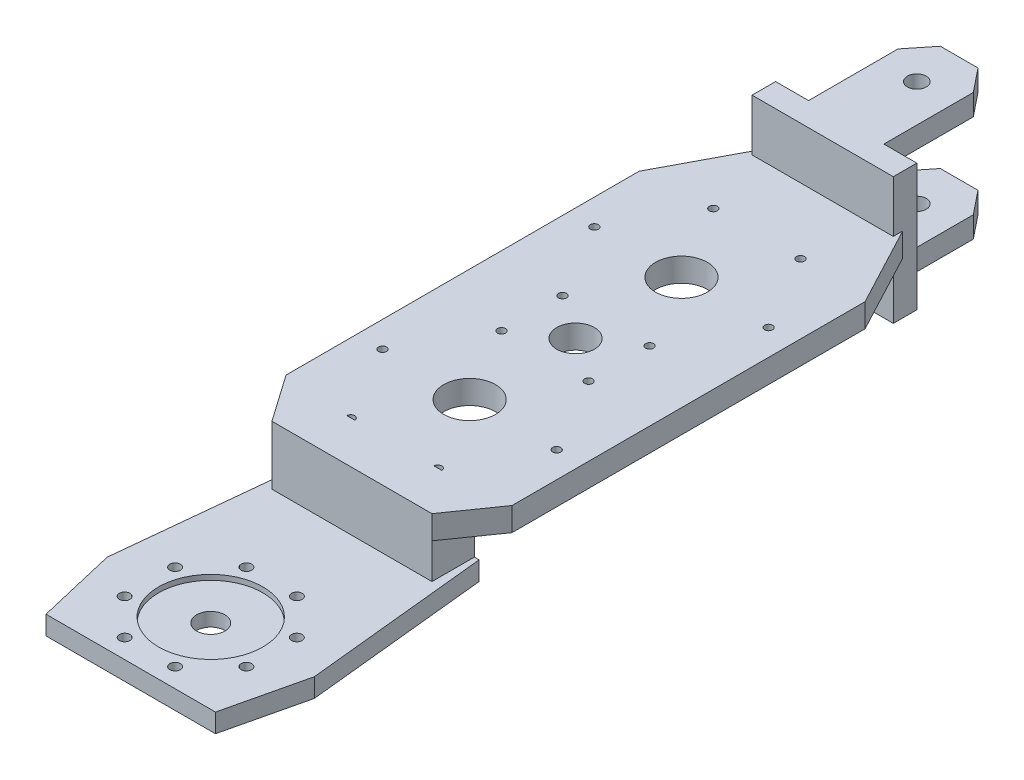
SolidWorks part; units mm, degrees
ref_plane "Front Plane" through (0, 0, 0) normal (0, 0, 1) x (1, 0, 0)
ref_plane "Top Plane" through (0, 0, 0) normal (0, 1, 0) x (1, 0, 0)
ref_plane "Right Plane" through (0, 0, 0) normal (1, 0, 0) x (0, 0, -1)
ref_plane "PL_Knee_Plate_base" through (0, -28, 0) normal (0, 1, 0) x (1, 0, 0)
sketch "SK_Knee_Plate" plane through (0, -28, 0) normal (0, 1, 0) x (1, 0, 0)
  line L0 (-36, -34) -> (36, -34)
  line L1 (36, -34) -> (44, 0)
  line L2 (44, 0) -> (36, 78)
  line L3 (36, 78) -> (-36, 78)
  line L4 (-36, 78) -> (-44, 0)
  line L5 (-44, 0) -> (-36, -34)
  circle A0 centre (25.8686, 10.7151) radius 2.25
  circle A1 centre (10.7151, 25.8686) radius 2.25
  circle A2 centre (-10.7151, 25.8686) radius 2.25
  circle A3 centre (-25.8686, 10.7151) radius 2.25
  circle A4 centre (-25.8686, -10.7151) radius 2.25
  circle A5 centre (-10.7151, -25.8686) radius 2.25
  circle A6 centre (10.7151, -25.8686) radius 2.25
  circle A7 centre (25.8686, -10.7151) radius 2.25
  circle A8 centre (0, 0) radius 6
  dimension "D11_SK_Knee_Plate" = 4.5
  dimension "D14_SK_Knee_Plate" = 4.5
  dimension "D17_SK_Knee_Plate" = 4.5
  dimension "D20_SK_Knee_Plate" = 4.5
  dimension "D23_SK_Knee_Plate" = 4.5
  dimension "D26_SK_Knee_Plate" = 4.5
  dimension "D29_SK_Knee_Plate" = 4.5
  dimension "D32_SK_Knee_Plate" = 4.5
  dimension "D35_SK_Knee_Plate" = 12
  dimension "P1" = 36
  dimension "P2" = 34
  dimension "P3" = 36
  dimension "P4" = 34
  dimension "P5" = 44
  dimension "P6" = 36
  dimension "P7" = 78
  dimension "P8" = 36
  dimension "P9" = 78
  dimension "P10" = 44
  dimension "P12" = 25.8686
  dimension "P13" = 10.7151
  dimension "P15" = 10.7151
  dimension "P16" = 25.8686
  dimension "P18" = 10.7151
  dimension "P19" = 25.8686
  dimension "P21" = 25.8686
  dimension "P22" = 10.7151
  dimension "P24" = 25.8686
  dimension "P25" = 10.7151
  dimension "P27" = 10.7151
  dimension "P28" = 25.8686
  dimension "P30" = 10.7151
  dimension "P31" = 25.8686
  dimension "P33" = 25.8686
  dimension "P34" = 10.7151
extrude "Knee_Plate" add sketch "SK_Knee_Plate" along normal blind 8
ref_plane "PL_Knee_Pilot_Recess_base" through (0, -20, 0) normal (0, 1, 0) x (1, 0, 0)
sketch "SK_Knee_Pilot_Recess" plane through (0, -20, 0) normal (0, 1, 0) x (1, 0, 0)
  circle A0 centre (0, 0) radius 22.15
  dimension "D1_SK_Knee_Pilot_Recess" = 44.3
extrude "Knee_Pilot_Recess" cut sketch "SK_Knee_Pilot_Recess" against normal blind 2.2
ref_plane "PL_Joggle_base" through (0, 0, -78) normal (0, 0, 1) x (1, 0, 0)
sketch "SK_Joggle" plane through (0, 0, -78) normal (0, 0, 1) x (1, 0, 0)
  line L0 (-34, -28) -> (34, -28)
  line L1 (34, -28) -> (34, 5)
  line L2 (34, 5) -> (-34, 5)
  line L3 (-34, 5) -> (-34, -28)
  dimension "P1" = 34
  dimension "P2" = 28
  dimension "P3" = 34
  dimension "P4" = 28
  dimension "P5" = 34
  dimension "P6" = 5
  dimension "P7" = 34
  dimension "P8" = 5
extrude "Joggle" add sketch "SK_Joggle" along normal blind 18
ref_plane "PL_Web_base" through (0, -5, 0) normal (0, 1, 0) x (1, 0, 0)
sketch "SK_Web" plane through (0, -5, 0) normal (0, 1, 0) x (1, 0, 0)
  line L0 (-34, 60) -> (34, 60)
  line L1 (34, 60) -> (48, 80)
  line L2 (48, 80) -> (48, 230)
  line L3 (48, 230) -> (30, 264)
  line L4 (30, 264) -> (-30, 264)
  line L5 (-30, 264) -> (-48, 230)
  line L6 (-48, 230) -> (-48, 80)
  line L7 (-48, 80) -> (-34, 60)
  circle A0 centre (37, 110) radius 1.7
  circle A1 centre (18.5, 142.0429) radius 1.7
  circle A2 centre (-18.5, 142.0429) radius 1.7
  circle A3 centre (-37, 110) radius 1.7
  circle A4 centre (-18.5, 77.9571) radius 1.7
  circle A5 centre (18.5, 77.9571) radius 1.7
  circle A6 centre (37, 200) radius 1.7
  circle A7 centre (18.5, 232.0429) radius 1.7
  circle A8 centre (-18.5, 232.0429) radius 1.7
  circle A9 centre (-37, 200) radius 1.7
  circle A10 centre (-18.5, 167.9571) radius 1.7
  circle A11 centre (18.5, 167.9571) radius 1.7
  circle A12 centre (0, 110) radius 11
  circle A13 centre (0, 200) radius 11
  circle A14 centre (0, 155) radius 8
  dimension "D17_SK_Web" = 3.4
  dimension "D20_SK_Web" = 3.4
  dimension "D23_SK_Web" = 3.4
  dimension "D26_SK_Web" = 3.4
  dimension "D29_SK_Web" = 3.4
  dimension "D32_SK_Web" = 3.4
  dimension "D35_SK_Web" = 3.4
  dimension "D38_SK_Web" = 3.4
  dimension "D41_SK_Web" = 3.4
  dimension "D44_SK_Web" = 3.4
  dimension "D47_SK_Web" = 3.4
  dimension "D50_SK_Web" = 3.4
  dimension "D53_SK_Web" = 22
  dimension "D55_SK_Web" = 22
  dimension "D57_SK_Web" = 16
  dimension "P1" = 34
  dimension "P2" = 60
  dimension "P3" = 34
  dimension "P4" = 60
  dimension "P5" = 48
  dimension "P6" = 80
  dimension "P7" = 48
  dimension "P8" = 230
  dimension "P9" = 30
  dimension "P10" = 264
  dimension "P11" = 30
  dimension "P12" = 264
  dimension "P13" = 48
  dimension "P14" = 230
  dimension "P15" = 48
  dimension "P16" = 80
  dimension "P18" = 37
  dimension "P19" = 110
  dimension "P21" = 18.5
  dimension "P22" = 142.0429
  dimension "P24" = 18.5
  dimension "P25" = 142.0429
  dimension "P27" = 37
  dimension "P28" = 110
  dimension "P30" = 18.5
  dimension "P31" = 77.9571
  dimension "P33" = 18.5
  dimension "P34" = 77.9571
  dimension "P36" = 37
  dimension "P37" = 200
  dimension "P39" = 18.5
  dimension "P40" = 232.0429
  dimension "P42" = 18.5
  dimension "P43" = 232.0429
  dimension "P45" = 37
  dimension "P46" = 200
  dimension "P48" = 18.5
  dimension "P49" = 167.9571
  dimension "P51" = 18.5
  dimension "P52" = 167.9571
  dimension "P54" = 110
  dimension "P56" = 200
  dimension "P58" = 155
extrude "Web" add sketch "SK_Web" along normal blind 10
ref_plane "PL_Fork_Bar_base" through (0, 0, -270) normal (0, 0, 1) x (1, 0, 0)
sketch "SK_Fork_Bar" plane through (0, 0, -270) normal (0, 0, 1) x (1, 0, 0)
  line L0 (-30, -27) -> (30, -27)
  line L1 (30, -27) -> (30, 27)
  line L2 (30, 27) -> (-30, 27)
  line L3 (-30, 27) -> (-30, -27)
  dimension "P1" = 30
  dimension "P2" = 27
  dimension "P3" = 30
  dimension "P4" = 27
  dimension "P5" = 30
  dimension "P6" = 27
  dimension "P7" = 30
  dimension "P8" = 27
extrude "Fork_Bar" add sketch "SK_Fork_Bar" along normal blind 10
ref_plane "PL_Tine_Lat_base" through (0, 18, 0) normal (0, 1, 0) x (1, 0, 0)
sketch "SK_Tine_Lat" plane through (0, 18, 0) normal (0, 1, 0) x (1, 0, 0)
  line L0 (-16, 260) -> (16, 260)
  line L1 (16, 260) -> (16, 308)
  line L2 (16, 308) -> (8, 318)
  line L3 (8, 318) -> (-8, 318)
  line L4 (-8, 318) -> (-16, 308)
  line L5 (-16, 308) -> (-16, 260)
  circle A0 centre (0, 300) radius 4
  dimension "D13_SK_Tine_Lat" = 8
  dimension "P1" = 16
  dimension "P2" = 260
  dimension "P3" = 16
  dimension "P4" = 260
  dimension "P5" = 16
  dimension "P6" = 308
  dimension "P7" = 8
  dimension "P8" = 318
  dimension "P9" = 8
  dimension "P10" = 318
  dimension "P11" = 16
  dimension "P12" = 308
  dimension "P14" = 300
extrude "Tine_Lat" add sketch "SK_Tine_Lat" along normal blind 9
ref_plane "PL_Tine_Med_base" through (0, -27, 0) normal (0, 1, 0) x (1, 0, 0)
sketch "SK_Tine_Med" plane through (0, -27, 0) normal (0, 1, 0) x (1, 0, 0)
  line L0 (-16, 260) -> (16, 260)
  line L1 (16, 260) -> (16, 308)
  line L2 (16, 308) -> (8, 318)
  line L3 (8, 318) -> (-8, 318)
  line L4 (-8, 318) -> (-16, 308)
  line L5 (-16, 308) -> (-16, 260)
  circle A0 centre (0, 300) radius 4
  dimension "D13_SK_Tine_Med" = 8
  dimension "P1" = 16
  dimension "P2" = 260
  dimension "P3" = 16
  dimension "P4" = 260
  dimension "P5" = 16
  dimension "P6" = 308
  dimension "P7" = 8
  dimension "P8" = 318
  dimension "P9" = 8
  dimension "P10" = 318
  dimension "P11" = 16
  dimension "P12" = 308
  dimension "P14" = 300
extrude "Tine_Med" add sketch "SK_Tine_Med" along normal blind 9
ref_plane "PL_AnkleZ" through (0, 0, -300) normal (0, 0, 1) x (1, 0, 0)
ref_axis "AX_AnklePitch" through (0, 29.75, -300) along (0, -1, 0)
ref_axis "AX_KneeY" through (0, 29.75, 0) along (0, -1, 0)
ref_plane "PL_KneeRef" through (0, 0, 0) normal (-0.9239, 0, 0.3827) x (0, -1, 0)
equation "\"Shin_length\" = 300"
equation "\"AnkleA_z\" = -110"
equation "\"AnkleB_z\" = -200"
